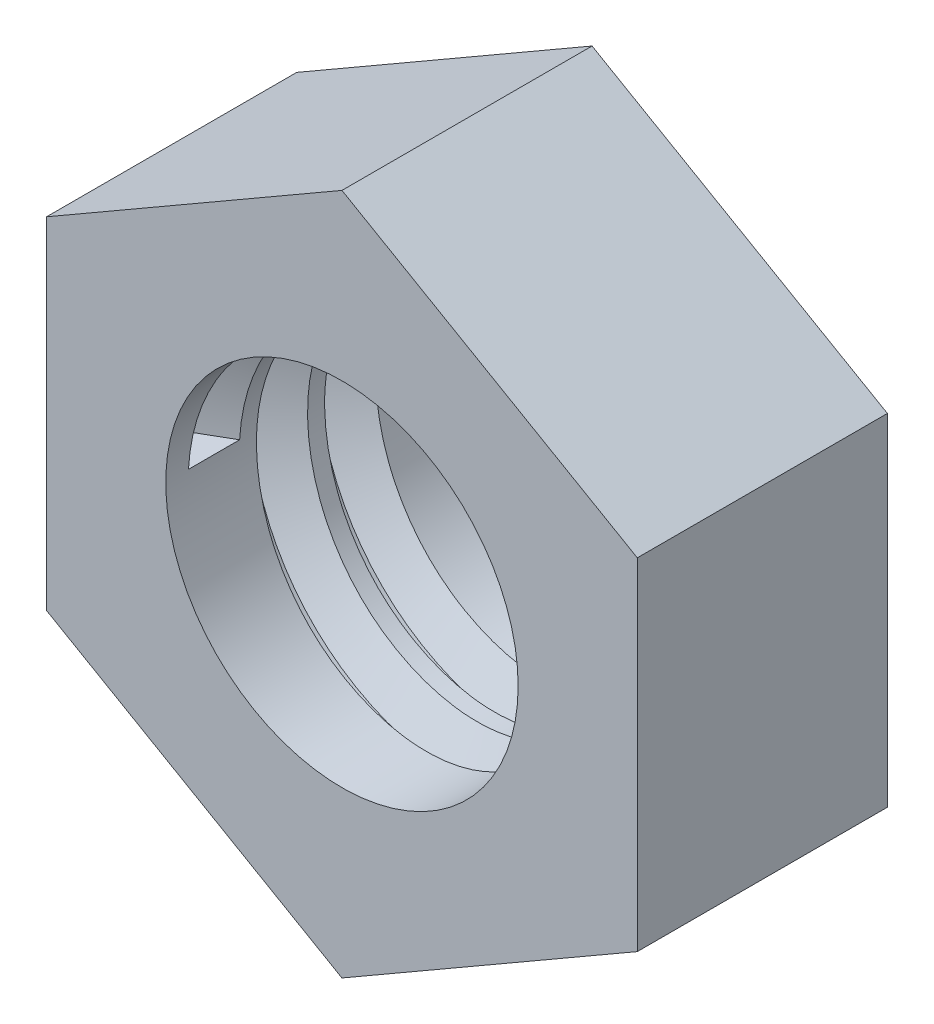
SolidWorks part; units mm, degrees
ref_plane "Front Plane" through (0, 0, 0) normal (0, 0, 1) x (1, 0, 0)
ref_plane "Top Plane" through (0, 0, 0) normal (0, 1, 0) x (1, 0, 0)
ref_plane "Right Plane" through (0, 0, 0) normal (1, 0, 0) x (0, 0, -1)
sketch "Sketch1" plane through (0, 0, 0) normal (0, 0, 1) x (1, 0, 0)
  line L1 (-2.5981, -1.5) -> (0, -3)
  line L2 (0, -3) -> (2.5981, -1.5)
  line L3 (2.5981, -1.5) -> (2.5981, 1.5)
  line L4 (2.5981, 1.5) -> (0, 3)
  line L5 (0, 3) -> (-2.5981, 1.5)
  line L6 (-2.5981, 1.5) -> (-2.5981, -1.5)
  circle A0 centre (0, 0) radius 2.5981 construction
  circle A1 centre (0, 0) radius 1.55
  dimension "D1" = 6
  dimension "D2" = 3.1
extrude "Boss-Extrude1" add sketch "Sketch1" along normal blind 2.2
thread "Thread1" pitch 0.6 method cut profile "Thread Profile1" start angle 0, offset 0.2, length 1.5, pitch 0.6, diameter 3.1
ref_plane "Plane1" through (-1.55, 0, 2) normal (0, -1, 0) x (-1, 0, 0)
sketch "Thread Profile1" plane through (-1.55, 0, 2) normal (0, -1, 0) x (-1, 0, 0)
  line L0 (0, 0) -> (0, 0.6) construction
  line L1 (0, 0) -> (0.3248, 0.1875)
  line L2 (0.3248, 0.1875) -> (0.3248, 0.2625)
  line L3 (0.3248, 0.2625) -> (0, 0.45)
  line L4 (0.3248, 0.225) -> (0, 0.225) construction
  line L11 (0, 0) -> (0, 0.45)
  point P2 (0, 0)
  dimension "Pitch" = 0.6
  dimension "Profile_Angle" = 60
  dimension "Profile_Land" = 0.075
  dimension "Profile_Height" = 0.3248
